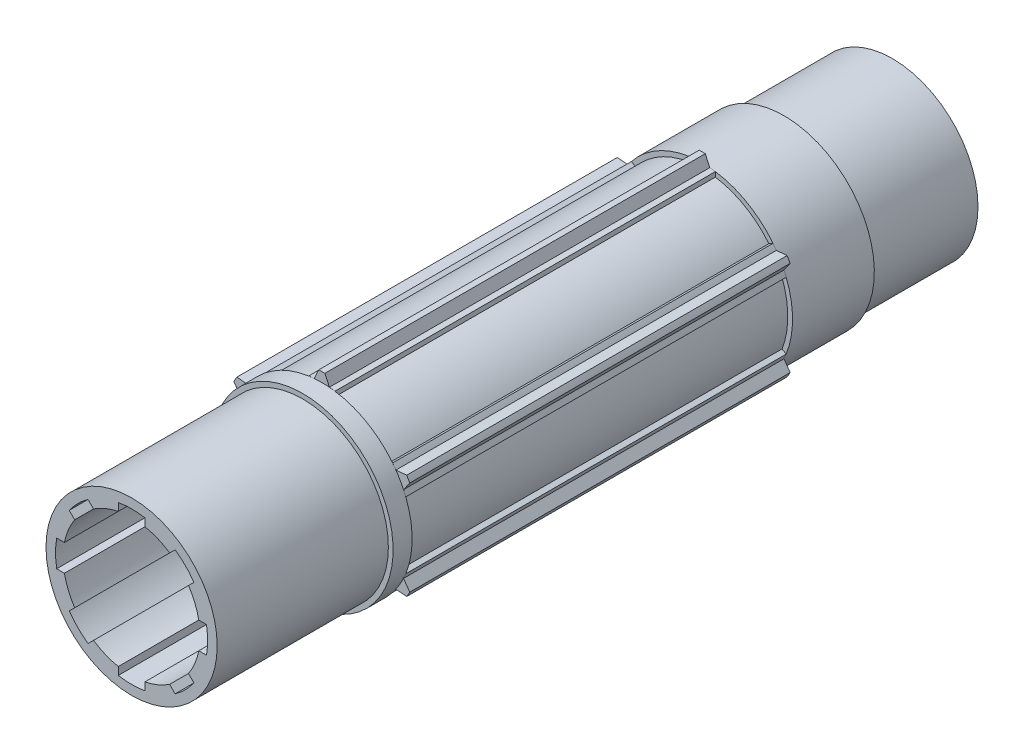
SolidWorks part; units mm, degrees
ref_plane "Front Plane" through (0, 0, 0) normal (0, 0, 1) x (1, 0, 0)
ref_plane "Top Plane" through (0, 0, 0) normal (0, 1, 0) x (1, 0, 0)
ref_plane "Right Plane" through (0, 0, 0) normal (1, 0, 0) x (0, 0, -1)
sketch "Sketch1" plane through (0, 0, 0) normal (0, 0, 1) x (1, 0, 0)
  line L0 (0, 0) -> (0, 33.7674) construction
  line L17 (-3.5, 19.6914) -> (-3.5, 17.6564)
  line L18 (3.5, 19.6914) -> (3.5, 17.6564)
  line L19 (11.449, 16.3988) -> (10.0101, 14.9599)
  line L20 (16.3988, 11.449) -> (14.9599, 10.0101)
  line L21 (19.6914, 3.5) -> (17.6564, 3.5)
  line L22 (19.6914, -3.5) -> (17.6564, -3.5)
  line L23 (16.3988, -11.449) -> (14.9599, -10.0101)
  line L24 (11.449, -16.3988) -> (10.0101, -14.9599)
  line L25 (3.5, -19.6914) -> (3.5, -17.6564)
  line L26 (-3.5, -19.6914) -> (-3.5, -17.6564)
  line L27 (-11.449, -16.3988) -> (-10.0101, -14.9599)
  line L28 (-16.3988, -11.449) -> (-14.9599, -10.0101)
  line L29 (-19.6914, -3.5) -> (-17.6564, -3.5)
  line L30 (-19.6914, 3.5) -> (-17.6564, 3.5)
  line L31 (-16.3988, 11.449) -> (-14.9599, 10.0101)
  line L32 (-11.449, 16.3988) -> (-10.0101, 14.9599)
  circle A17 centre (0, 0) radius 22.5
  arc A18 (-11.449, 16.3988) -> (-16.3988, 11.449) centre (0, 0) ccw
  arc A19 (-3.5, 17.6564) -> (-10.0101, 14.9599) centre (0, 0) ccw
  arc A20 (3.5, 19.6914) -> (-3.5, 19.6914) centre (0, 0) ccw
  arc A21 (10.0101, 14.9599) -> (3.5, 17.6564) centre (0, 0) ccw
  arc A22 (-14.9599, 10.0101) -> (-17.6564, 3.5) centre (0, 0) ccw
  arc A23 (-19.6914, 3.5) -> (-19.6914, -3.5) centre (0, 0) ccw
  arc A24 (-17.6564, -3.5) -> (-14.9599, -10.0101) centre (0, 0) ccw
  arc A25 (-16.3988, -11.449) -> (-11.449, -16.3988) centre (0, 0) ccw
  arc A26 (-10.0101, -14.9599) -> (-3.5, -17.6564) centre (0, 0) ccw
  arc A27 (-3.5, -19.6914) -> (3.5, -19.6914) centre (0, 0) ccw
  arc A28 (3.5, -17.6564) -> (10.0101, -14.9599) centre (0, 0) ccw
  arc A29 (11.449, -16.3988) -> (16.3988, -11.449) centre (0, 0) ccw
  arc A30 (14.9599, -10.0101) -> (17.6564, -3.5) centre (0, 0) ccw
  arc A31 (19.6914, -3.5) -> (19.6914, 3.5) centre (0, 0) ccw
  arc A32 (17.6564, 3.5) -> (14.9599, 10.0101) centre (0, 0) ccw
  arc A33 (16.3988, 11.449) -> (11.449, 16.3988) centre (0, 0) ccw
  point P39 (0, 0)
  dimension "D1" = 3.5
  dimension "D2" = 3.5
extrude "Boss-Extrude1" add sketch "Sketch1" along normal blind 200
sketch "Sketch3" plane through (0, 0, 0) normal (0, 0, 1) x (1, 0, 0)
  line L0 (0, 0) -> (0, 28.873) construction
  line L1 (-2, 23.666) -> (-0.8008, 26.2378)
  line L2 (2, 23.666) -> (0.8008, 26.2378)
  line L3 (-3.4611, 21.9792) -> (-3.4611, 23.4968)
  line L4 (3.4611, 21.9792) -> (3.4611, 23.4968)
  line L5 (17.304, 13.987) -> (18.6183, 14.7458)
  line L6 (19.4953, 13.5651) -> (22.3222, 13.8124)
  line L7 (21.4953, 10.1009) -> (23.123, 12.4254)
  line L8 (20.7651, 7.9922) -> (22.0794, 8.751)
  line L9 (20.7651, -7.9922) -> (22.0794, -8.751)
  line L10 (21.4953, -10.1009) -> (23.123, -12.4254)
  line L11 (19.4953, -13.5651) -> (22.3222, -13.8124)
  line L12 (17.304, -13.987) -> (18.6183, -14.7458)
  line L13 (3.4611, -21.9792) -> (3.4611, -23.4968)
  line L14 (2, -23.666) -> (0.8008, -26.2378)
  line L15 (-2, -23.666) -> (-0.8008, -26.2378)
  line L16 (-3.4611, -21.9792) -> (-3.4611, -23.4968)
  line L17 (-17.304, -13.987) -> (-18.6183, -14.7458)
  line L18 (-19.4953, -13.5651) -> (-22.3222, -13.8124)
  line L19 (-21.4953, -10.1009) -> (-23.123, -12.4254)
  line L20 (-20.7651, -7.9922) -> (-22.0794, -8.751)
  line L21 (-20.7651, 7.9922) -> (-22.0794, 8.751)
  line L22 (-21.4953, 10.1009) -> (-23.123, 12.4254)
  line L23 (-19.4953, 13.5651) -> (-22.3222, 13.8124)
  line L24 (-17.304, 13.987) -> (-18.6183, 14.7458)
  arc A0 (-20.7651, -7.9922) -> (-17.304, -13.987) centre (0, 0) ccw
  arc A1 (-2, 23.666) -> (-3.4611, 23.4968) centre (0, 0) ccw
  arc A2 (0.8008, 26.2378) -> (-0.8008, 26.2378) centre (0, 0) ccw
  arc A3 (2, 23.666) -> (3.4611, 23.4968) centre (0, 0) cw
  arc A4 (19.4953, 13.5651) -> (18.6183, 14.7458) centre (0, 0) ccw
  arc A5 (23.123, 12.4254) -> (22.3222, 13.8124) centre (0, 0) ccw
  arc A6 (21.4953, 10.1009) -> (22.0794, 8.751) centre (0, 0) cw
  arc A7 (21.4953, -10.1009) -> (22.0794, -8.751) centre (0, 0) ccw
  arc A8 (22.3222, -13.8124) -> (23.123, -12.4254) centre (0, 0) ccw
  arc A9 (19.4953, -13.5651) -> (18.6183, -14.7458) centre (0, 0) cw
  arc A10 (2, -23.666) -> (3.4611, -23.4968) centre (0, 0) ccw
  arc A11 (-0.8008, -26.2378) -> (0.8008, -26.2378) centre (0, 0) ccw
  arc A12 (-2, -23.666) -> (-3.4611, -23.4968) centre (0, 0) cw
  arc A13 (-19.4953, -13.5651) -> (-18.6183, -14.7458) centre (0, 0) ccw
  arc A14 (-23.123, -12.4254) -> (-22.3222, -13.8124) centre (0, 0) ccw
  arc A15 (-21.4953, -10.1009) -> (-22.0794, -8.751) centre (0, 0) cw
  arc A16 (-21.4953, 10.1009) -> (-22.0794, 8.751) centre (0, 0) ccw
  arc A17 (-22.3222, 13.8124) -> (-23.123, 12.4254) centre (0, 0) ccw
  arc A18 (-19.4953, 13.5651) -> (-18.6183, 14.7458) centre (0, 0) cw
  arc A19 (-17.304, 13.987) -> (-20.7651, 7.9922) centre (0, 0) ccw
  arc A20 (3.4611, 21.9792) -> (-3.4611, 21.9792) centre (0, 0) ccw
  arc A21 (20.7651, 7.9922) -> (17.304, 13.987) centre (0, 0) ccw
  arc A22 (17.304, -13.987) -> (20.7651, -7.9922) centre (0, 0) ccw
  arc A23 (-3.4611, -21.9792) -> (3.4611, -21.9792) centre (0, 0) ccw
  point P55 (0, 0)
  dimension "D1" = 44.5
extrude "Boss-Extrude2" add sketch "Sketch3" along normal blind 100 from offset 50
sketch "Sketch4" plane through (0, 0, 200) normal (0, 0, 1) x (1, 0, 0)
  circle A0 centre (0, 0) radius 23.75
  circle A1 centre (0, 0) radius 22.25
  dimension "D1" = 44.5
  dimension "D2" = 47.5
extrude "Boss-Extrude3" add sketch "Sketch4" along normal blind 5 from surface starting at face at (20.7379, 11.973, 150)
extrude "Boss-Extrude4" add sketch "Sketch4<2>" against normal blind 21.5 from surface starting at face at (0, 23.946, 50)
sketch "Sketch4<2>" plane through (0, 0, 200) normal (0, 0, 1) x (1, 0, 0) same geometry as "Sketch4"
